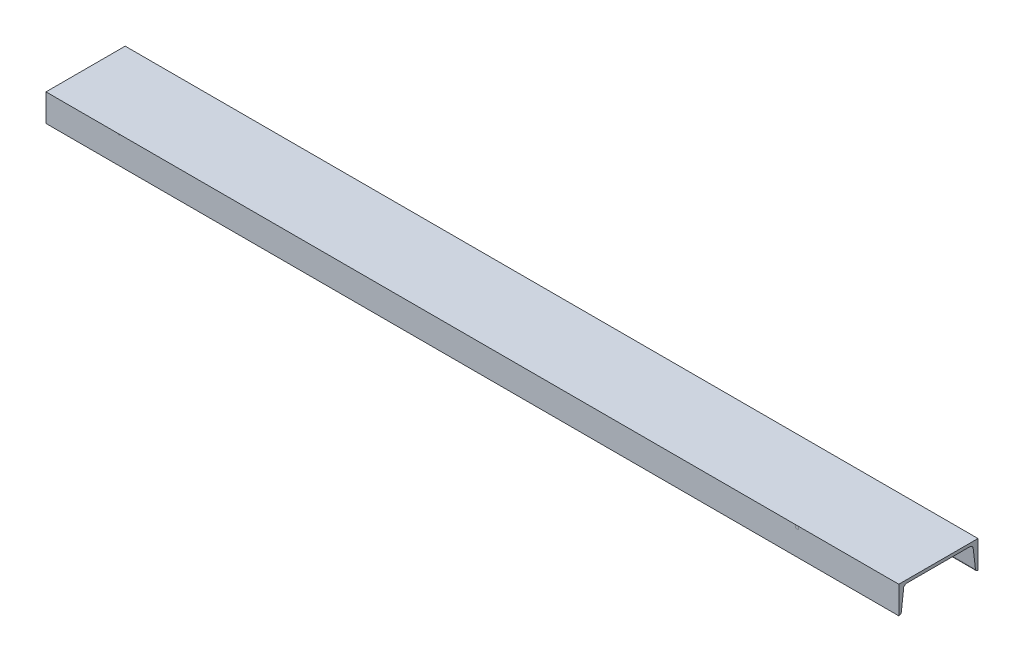
SolidWorks part; units mm, degrees
ref_plane "Спереди" through (0, 0, 0) normal (0, 0, 1) x (1, 0, 0)
ref_plane "Сверху" through (0, 0, 0) normal (0, 1, 0) x (1, 0, 0)
ref_plane "Справа" through (0, 0, 0) normal (1, 0, 0) x (0, 0, -1)
sketch "Эскиз2" plane through (0, 0, 0) normal (1, 0, 0) x (0, 0, -1)
  line L0 (130, 0) -> (-130, 0)
  line L1 (-130, 0) -> (-130, -90)
  line L2 (0, 0) -> (0, -100) construction
  line L3 (101.8373, -10) -> (-101.8373, -10)
  line L4 (-113.796, -16.7206) -> (-121.7267, -83.8216)
  line L5 (-130, -90) -> (-128.6783, -90)
  line L6 (130, -90) -> (128.6783, -90)
  line L7 (113.796, -16.7206) -> (121.7267, -83.8216)
  line L8 (130, 0) -> (130, -90)
  arc A0 (-101.8373, -10) -> (-113.796, -16.7206) centre (-101.8373, -24) ccw
  arc A1 (-128.6783, -90) -> (-121.7267, -83.8216) centre (-128.6783, -83) ccw
  arc A2 (128.6783, -90) -> (121.7267, -83.8216) centre (128.6783, -83) cw
  arc A3 (101.8373, -10) -> (113.796, -16.7206) centre (101.8373, -24) cw
  point P19 (0, -10)
extrude "Бобышка-Вытянуть1" add sketch "Эскиз2" along normal blind 2800
sketch "Эскиз3" plane through (0, 0, 130) normal (0, 0, 1) x (1, 0, 0)
  line L2 (241.3761, 0) -> (237.9643, 0)
  line L3 (241.3761, 0) -> (241.3761, -3.4118)
  line L4 (241.3761, -3.4118) -> (237.9643, -3.4118)
  line L5 (237.9643, 0) -> (237.9643, -3.4118)
extrude "Вырез-Вытянуть1" cut sketch "Эскиз3" against normal blind 0.01
sketch "Эскиз4" plane through (0, 0, 130) normal (0, 0, 1) x (1, 0, 0)
  line L0 (2800, 0) -> (241.3761, 0) construction
  line L1 (2460, 0) -> (2470, 0)
  line L2 (2460, 0) -> (2460, -10)
  line L3 (2460, -10) -> (2470, -10)
  line L4 (2470, 0) -> (2470, -10)
extrude "Бобышка-Вытянуть2" add sketch "Эскиз4" against normal blind 0.01
extrude "Вырез-Вытянуть2" cut sketch "Эскиз4<2>" against normal blind 0.01
sketch "Эскиз4<2>" plane through (0, 0, 130) normal (0, 0, 1) x (1, 0, 0) same geometry as "Эскиз4"
